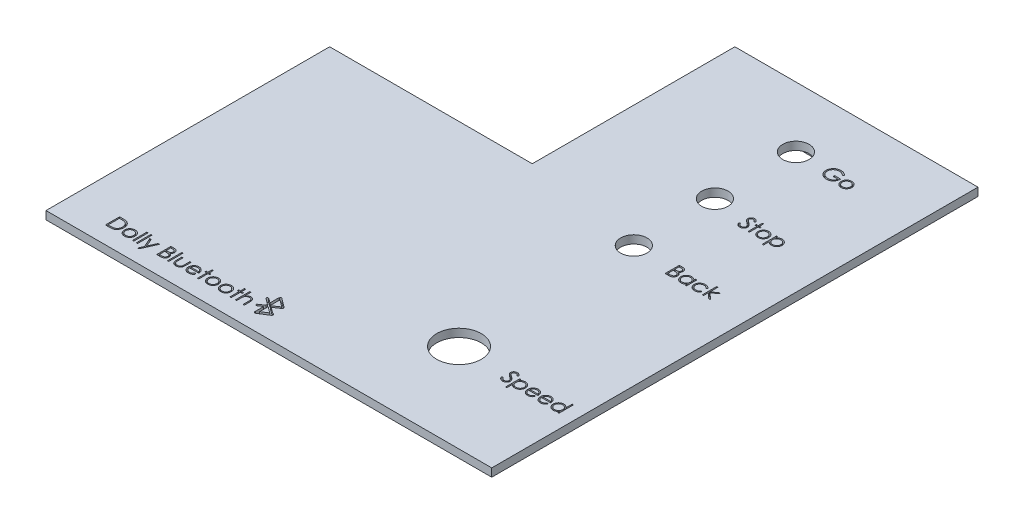
SolidWorks part; units mm, degrees
ref_plane "Alzado" through (0, 0, 0) normal (0, 0, 1) x (1, 0, 0)
ref_plane "Planta" through (0, 0, 0) normal (0, 1, 0) x (1, 0, 0)
ref_plane "Vista lateral" through (0, 0, 0) normal (1, 0, 0) x (0, 0, -1)
sketch "Croquis1" plane through (0, 0, 0) normal (0, 1, 0) x (1, 0, 0)
  line L2 (0, 0) -> (0, 50)
  line L3 (0, 50) -> (60, 50)
  line L4 (60, 0) -> (60, 50)
  line L5 (0, 0) -> (-50, 0)
  line L6 (60, 0) -> (60, -70)
  line L7 (60, -70) -> (-50, -70)
  line L8 (-50, 0) -> (-50, -70)
  dimension "D1" = 60
  dimension "D2" = 110
  dimension "D3" = 120
  dimension "D4" = 50
extrude "Saliente-Extruir1" add sketch "Croquis1" along normal blind 3
sketch "Croquis2" plane through (0, 3, 0) normal (0, 1, 0) x (1, 0, 0)
  line L0 (30, 50) -> (30, -90.8988) construction
  line L1 (60, 50) -> (0, 50) construction
  circle A0 centre (30, -48.0782) radius 5.5
  circle A1 centre (30, -4.9351) radius 3.25
  circle A2 centre (30, 15.0649) radius 3.25
  circle A3 centre (30, 35.0649) radius 3.25
  dimension "D1" = 6.5
  dimension "D2" = 6.5
  dimension "D3" = 6.5
  dimension "D6" = 11
  dimension "D4" = 20
  dimension "D5" = 20
extrude "Cortar-Extruir1" cut sketch "Croquis2" against normal blind 10
sketch "Croquis4" plane through (0, 3, 0) normal (0, 1, 0) x (1, 0, 0)
  text T0 "Atrás"
  text T1 "Parar\r\n"
  text T2 "Adelante\r\n"
  text T3 "Speed\r\n\r\n"
extrude "Cortar-Extruir2" cut sketch "Croquis4" against normal blind 1
sketch "Croquis5" plane through (0, 0, 0) normal (0, -1, 0) x (-1, 0, 0)
  line L0 (45, -65) -> (45, -5)
  line L1 (45, -5) -> (-5, -5)
  line L2 (-5, -5) -> (-5, 45)
  line L3 (-5, 45) -> (-55, 45)
  line L4 (-55, 45) -> (-55, -65)
  line L5 (-55, -65) -> (45, -65)
  line L6 (50, 0) -> (50, -70) construction
  line L7 (50, -70) -> (-60, -70) construction
  line L9 (-60, -70) -> (-60, 50) construction
  line L10 (-60, 50) -> (0, 50) construction
  line L11 (0, 50) -> (0, 0) construction
  line L12 (0, 0) -> (50, 0) construction
  line L13 (42, -62) -> (-52, -62)
  line L14 (-52, -62) -> (-52, 42)
  line L15 (-52, 42) -> (-8, 42)
  line L16 (-8, 42) -> (-8, -8)
  line L17 (-8, -8) -> (42, -8)
  line L18 (42, -8) -> (42, -62)
  dimension "D1" = 5
  dimension "D2" = 5
  dimension "D3" = 5
  dimension "D4" = 5
  dimension "D5" = 5
  dimension "D6" = 5
  dimension "D7" = 3
  dimension "D8" = 3
  dimension "D9" = 3
  dimension "D10" = 3
  dimension "D11" = 3
  dimension "D12" = 3
extrude "Saliente-Extruir2" add sketch "Croquis5" along normal blind 4
sketch "Croquis7" plane through (0, 2, 0) normal (0, 1, 0) x (1, 0, 0)
  text T0 "Dolly Bluetooth"
extrude "Cortar-Extruir3" cut sketch "Croquis7" against normal blind 1
sketch "Croquis8" plane through (0, 2, 0) normal (0, 1, 0) x (1, 0, 0)
  line L0 (-2.3317, -62.93) -> (-2.3317, -62.8822) construction
  line L1 (-2.6308, -65.6692) -> (-2.6308, -63.6453)
  line L2 (-2.0326, -65.2301) -> (-2.0326, -63.1487)
  line L4 (-2.2116, -59.6051) -> (0.1201, -61.34)
  line L5 (-2.0326, -60.2398) -> (-0.3171, -61.5162)
  line L6 (-2.6308, -63.0851) -> (-3.9057, -63.9495)
  line L7 (0.0101, -61.8546) -> (-1.53, -62.899)
  line L8 (-0.3171, -61.5162) -> (-1.9277, -62.6083)
  line L10 (-3.7587, -61.2698) -> (-2.6308, -62.0943)
  line L11 (-4.0527, -61.6719) -> (-2.6308, -62.7113)
  line L13 (0.186, -64.6126) -> (-2.1558, -66.0879)
  line L14 (-0.5032, -64.2667) -> (-2.0326, -65.2301)
  line L15 (-2.0326, -62.5316) -> (-1.9277, -62.6083)
  line L16 (-1.9478, -62.9021) -> (-1.9413, -62.9068) construction
  line L19 (-2.6308, -63.6453) -> (-3.6454, -64.3333)
  line L21 (-2.6308, -62.0943) -> (-2.6308, -60.0656)
  line L23 (-2.0326, -63.1487) -> (-0.5032, -64.2667)
  line L24 (-1.9478, -62.9021) -> (-1.9413, -62.9068) construction
  line L25 (-2.0326, -62.5316) -> (-2.0326, -60.2398)
  line L27 (-2.6308, -63.0851) -> (-2.6308, -62.7113)
  line L28 (-1.53, -62.899) -> (-0.0177, -64.0045)
  arc A2 (-2.2116, -59.6051) -> (-2.5211, -59.8341) centre (-2.3317, -59.7665) ccw
  arc A3 (0.1117, -61.6686) -> (0.1201, -61.34) centre (0, -61.5014) ccw
  arc A4 (0.0101, -61.8546) -> (0.1117, -61.6686) centre (-0.1201, -61.6627) ccw
  arc A5 (-3.9057, -63.9495) -> (-3.6454, -64.3333) centre (-3.7756, -64.1414) ccw
  arc A6 (-3.7587, -61.2698) -> (-4.0527, -61.6719) centre (-3.9057, -61.4708) ccw
  arc A8 (0.186, -64.6126) -> (-0.0177, -64.0045) centre (0.0101, -64.3333) ccw
  arc A9 (-2.6308, -65.6692) -> (-2.1558, -66.0879) centre (-2.3317, -65.8086) ccw
  arc A10 (-2.5211, -59.8341) -> (-2.6308, -60.0656) centre (-2.3317, -60.0656) ccw
  point P2 (-2.3317, -62.9371)
  point P7 (-1.1658, -60.6339)
  point P14 (-1.9478, -62.9021)
  point P23 (-1.9478, -62.9021)
  point P28 (-1.1608, -65.071)
extrude "Cortar-Extruir5" cut sketch "Croquis8" against normal blind 1
sketch "Croquis9" plane through (0, 2, 0) normal (0, 1, 0) x (1, 0, 0)
  text T0 "Go"
extrude "Cortar-Extruir6" cut sketch "Croquis9" against normal blind 1
sketch "Croquis10" plane through (0, 2, 0) normal (0, 1, 0) x (1, 0, 0)
  text T0 "Stop"
extrude "Cortar-Extruir7" cut sketch "Croquis10" against normal blind 1
sketch "Croquis11" plane through (0, 2, 0) normal (0, 1, 0) x (1, 0, 0)
  text T0 "Back"
extrude "Cortar-Extruir8" cut sketch "Croquis11" against normal blind 1
sketch "Croquis12" plane through (0, 2, 0) normal (0, 1, 0) x (1, 0, 0)
  text T0 "Speed"
extrude "Cortar-Extruir9" cut sketch "Croquis12" against normal blind 1
